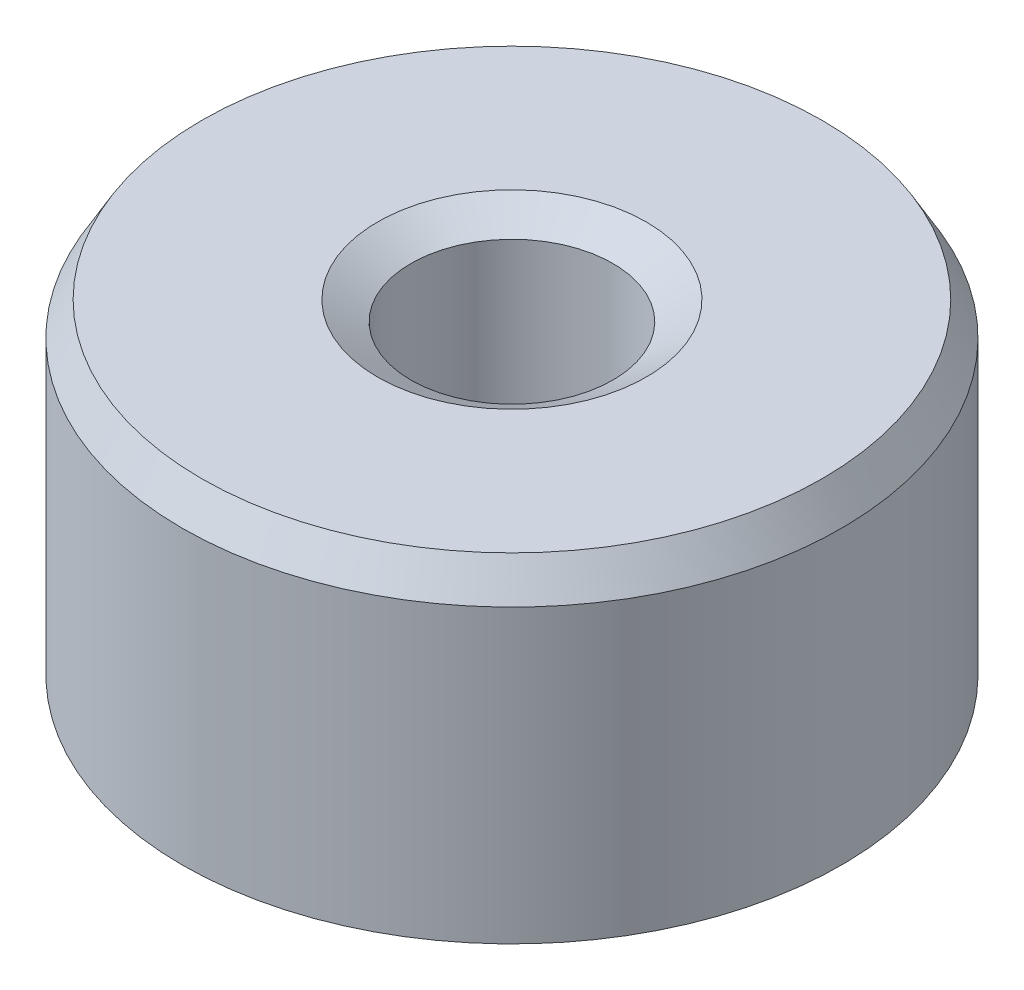
SolidWorks part; units mm, degrees
ref_plane "Front Plane" through (0, 0, 0) normal (0, 0, 1) x (1, 0, 0)
ref_plane "Top Plane" through (0, 0, 0) normal (0, 1, 0) x (1, 0, 0)
ref_plane "Right Plane" through (0, 0, 0) normal (1, 0, 0) x (0, 0, -1)
sketch "Sketch1" plane through (0, 0, 0) normal (0, 1, 0) x (1, 0, 0)
  circle A0 centre (0, 0) radius 7.5
  dimension "SLEEVE_OD" = 15
extrude "Boss-Extrude1" add sketch "Sketch1" along normal blind 7.8352
sketch "Sketch2" plane through (0, 0, 0) normal (0, 1, 0) x (1, 0, 0)
  circle A0 centre (0, 0) radius 2.2993
  dimension "BORE_D" = 4.5986
extrude "Cut-Extrude1" cut sketch "Sketch2" along normal through all
chamfer "Chamfer1" distance 0.7592 angle 30 4 edges at (0, 7.8352, 2.2993) (0, 0, 2.2993) (0, 0, 7.5) (0, 7.8352, 7.5) first distance on face at (0, 7.8352, 2.2993) first distance on face at (0, 0, 2.2993) first distance on face at (0, 7.8352, 7.5)
